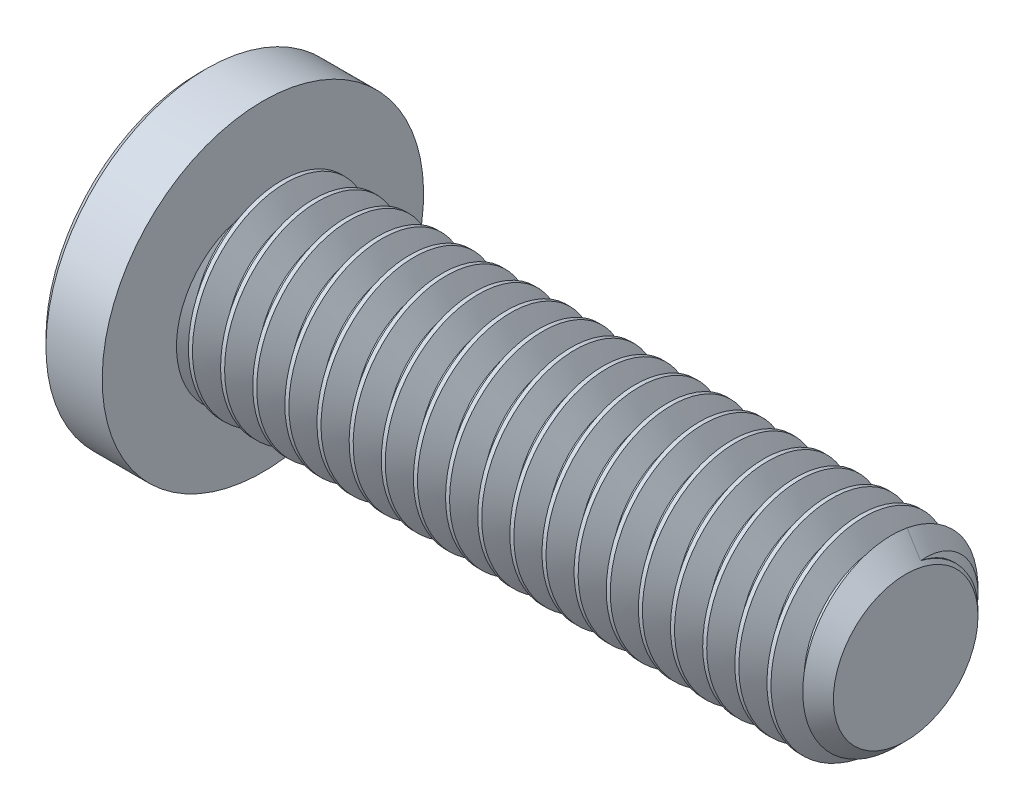
SolidWorks part; units mm, degrees
ref_plane "Front Plane" through (0, 0, 0) normal (0, 0, 1) x (1, 0, 0)
ref_plane "Top Plane" through (0, 0, 0) normal (0, 1, 0) x (1, 0, 0)
ref_plane "Right Plane" through (0, 0, 0) normal (1, 0, 0) x (0, 0, -1)
sketch "Sketch1" plane through (0, 0, 0) normal (0, 0, 1) x (1, 0, 0)
  line L0 (10, 0) -> (-10, 0) construction
  line L1 (10, 3) -> (10, -3) construction
  line L2 (-10, 5) -> (-10, -5) construction
  line L3 (-10, 5) -> (-11.75, 5) construction
  line L4 (-11.75, 5) -> (-12, 4.75) construction
  line L5 (-12, 4.75) -> (-12, -4.75) construction
  line L6 (-12, -4.75) -> (-11.75, -5) construction
  line L7 (-11.75, -5) -> (-10, -5) construction
  point P7 (-8.88, 0)
  point P12 (6, -3)
  dimension "D1" = 45
  dimension "Dec." = 6
  dimension "Length" = 20
  dimension "Head Dia" = 10
  dimension "Head Height" = 2
  dimension "Hex Depth" = 3.12
  dimension "Chamfer" = 0.25
  dimension "D2" = 4
ref_plane "Plane1" through (10, 0, 0) normal (1, 0, 0) x (0, 0, -1)
ref_plane "Plane2" through (-12, 0, 0) normal (1, 0, 0) x (0, 0, -1)
sketch "Sketch2" plane through (10, 0, 0) normal (1, 0, 0) x (0, 0, -1)
  circle A0 centre (0, 0) radius 3
extrude "Boss-Extrude1" add sketch "Sketch2" against normal up to vertex (20 mm away) up to point (-10, 0, 0)
sketch "Sketch3" plane through (10, 0, 0) normal (1, 0, 0) x (0, 0, -1)
  circle A0 centre (0, 0) radius 3 construction
  circle A1 centre (0, 0) radius 3
curve "Helix/Spiral1" pitch 1 height 21 radius 3 centre (10, 0, 0) axis (-1, 0, 0) start towards (0, 1, 0) parameters "Pitch"=1
chamfer "Chamfer1" distance 0.75 angle 45 1 edges at (10, 0, -3)
sketch "Sketch5" plane through (0, 0, 0) normal (0, 0, 1) x (1, 0, 0)
  line L0 (9.5625, 3) -> (10.4375, 3)
  line L1 (10.4375, 3) -> (10.0625, 2.3505)
  line L2 (10.0625, 2.3505) -> (9.9375, 2.3505)
  line L3 (9.9375, 2.3505) -> (9.5625, 3)
  line L4 (10, 2.3505) -> (10, 3) construction
  line L5 (9.75, 2.6752) -> (10.25, 2.6752) construction
  dimension "D1" = 60
  dimension "D2" = 0.5
  dimension "D3" = 0.125
sweep "Cut-Sweep1" cut profiles "Sketch5" path "Helix/Spiral1" align with end faces yes
sketch "Sketch4" plane through (-12, 0, 0) normal (1, 0, 0) x (0, 0, -1)
  line L0 (-5, 0.7937) -> (5, 0.7937) construction
  line L1 (0, 2.3094) -> (-2, 1.1547)
  line L2 (-2, 1.1547) -> (-2, -1.1547)
  line L3 (-2, -1.1547) -> (0, -2.3094)
  line L4 (0, -2.3094) -> (2, -1.1547)
  line L5 (2, -1.1547) -> (2, 1.1547)
  line L6 (2, 1.1547) -> (0, 2.3094)
  line L7 (0, 0) -> (0, 0.7937) construction
  circle A0 centre (0, 0) radius 2 construction
  dimension "Hex Size" = 4
  dimension "D1" = 10
  dimension "D2" = 0.7937
sketch "Sketch6" plane through (0, 0, 0) normal (0, 0, 1) x (1, 0, 0)
  line L0 (-11.75, 5) -> (-12, 4.75) construction
  line L1 (-10, 5) -> (-11.75, 5) construction
  line L2 (-10, 5) -> (-10, -5) construction
  line L3 (-12, 4.75) -> (-12, -4.75) construction
  line L4 (-11.75, 5) -> (-12, 4.75)
  line L5 (-10, 5) -> (-11.75, 5)
  line L6 (-10, 5) -> (-10, 0)
  line L7 (-12, 4.75) -> (-12, 0)
  line L8 (-10, 0) -> (-12, 0) construction
  line L9 (-10, 0) -> (-12, 0)
revolve "Revolve1" add sketch "Sketch6" angle 360 about L8
extrude "Cut-Extrude1" cut sketch "Sketch4" along normal up to vertex (3.12 mm away) up to point (-8.88, 0, 0)
sketch "Sketch8" plane through (-12, 0, 0) normal (-1, 0, 0) x (0, 0, 1)
  circle A1 centre (0, 0) radius 2.3094
extrude "Cut-Extrude2" cut sketch "Sketch8" against normal through all draft 45
equation "\"D3@Helix/Spiral1\" = \"Length@Sketch1\"+\"Pitch@Helix/Spiral1\""
equation "\"D3@Sketch5\" = \"Pitch@Helix/Spiral1\"*.125"
equation "\"D2@Sketch5\" = \"Pitch@Helix/Spiral1\"*.50"
equation "\"D1@Chamfer1\" = \"Pitch@Helix/Spiral1\"*.75"
equation "\"D2@Sketch1\" = \"Pitch@Helix/Spiral1\"*4"
equation "\"D1@Sketch4\" = \"Head Dia@Sketch1\""
equation "\"Chamfer@Sketch1\" = \"Head Height@Sketch1\"/8"
